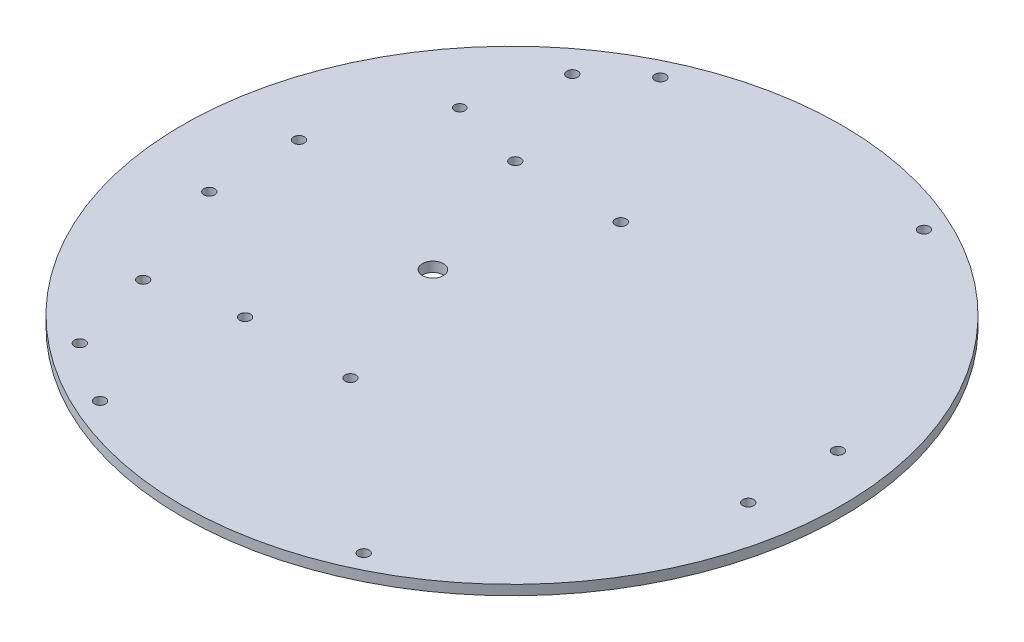
SolidWorks part; units mm, degrees
ref_plane "Alzado" through (0, 0, 0) normal (0, 0, 1) x (1, 0, 0)
ref_plane "Planta" through (0, 0, 0) normal (0, 1, 0) x (1, 0, 0)
ref_plane "Vista lateral" through (0, 0, 0) normal (1, 0, 0) x (0, 0, -1)
sketch "Croquis1" plane through (0, 0, 0) normal (0, 1, 0) x (1, 0, 0)
  line L0 (0, 0) -> (-88.4646, 0) construction
  line L1 (-88.4646, 0) -> (-72.2, -60.7004) construction
  line L5 (-88.4646, 0) -> (-88.4646, -58.7493) construction
  line L6 (-88.0486, -1.5529) -> (-71.8401, 49.51) construction
  line L8 (-72.2, 15.6777) -> (-72.2, -15.7875) construction
  line L10 (0, 0) -> (0, -71.6257) construction
  line L12 (72.2, 15.6777) -> (72.2, -15.7875) construction
  circle A15 centre (40, -85) radius 1.65
  circle A16 centre (40, 85) radius 1.65
  circle A19 centre (0, 0) radius 100
  circle A25 centre (-40, -85) radius 1.65
  circle A28 centre (-40, 85) radius 1.65
  circle A29 centre (-40, 41) radius 1.65
  circle A30 centre (-40, -41) radius 1.65
  circle A31 centre (-24, 0) radius 3.175
  circle A32 centre (-8, 41) radius 1.65
  circle A33 centre (-8, -41) radius 1.65
  circle A34 centre (85.0702, 13.8244) radius 1.65
  circle A36 centre (85.0702, -13.3756) radius 1.65
  circle A38 centre (-54.2275, 72.5284) radius 1.65
  circle A39 centre (-62.4567, 46.6031) radius 1.5598
  circle A40 centre (-78.397, 13.7523) radius 1.65
  circle A41 centre (-78.397, -13.4477) radius 1.65
  circle A42 centre (-65.2783, -46.6361) radius 1.65
  circle A43 centre (-58.2384, -72.9093) radius 1.65
  point P17 (0, 0)
  point P72 (0, 0)
  dimension "D10" = 200
  dimension "D14" = 41
  dimension "D3" = 40
  dimension "D7" = 3.3
  dimension "D13" = 24
  dimension "D16" = 41
  dimension "D2" = 85
  dimension "D18" = 8
  dimension "D5" = 40
  dimension "D12" = 6.35
  dimension "D4" = 85
  dimension "D6" = 40
  dimension "D8" = 40
  dimension "D9" = 85
  dimension "D11" = 85
  dimension "D15" = 41
  dimension "D17" = 41
  dimension "D19" = 15
extrude "Saliente-Extruir1" add sketch "Croquis1" along normal blind 3
